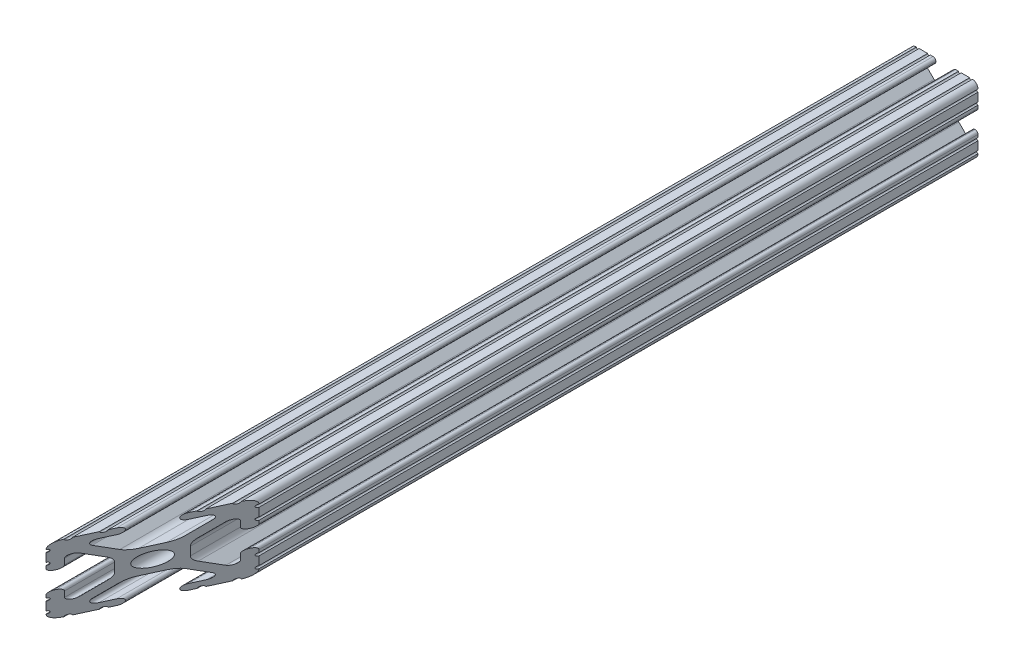
SolidWorks part; units mm, degrees
ref_plane "Front Plane" through (0, 0, 0) normal (0, 0, 1) x (1, 0, 0)
ref_plane "Top Plane" through (0, 0, 0) normal (0, 1, 0) x (1, 0, 0)
ref_plane "Right Plane" through (0, 0, 0) normal (1, 0, 0) x (0, 0, -1)
sketch "Sketch1" plane through (0, 0, 0) normal (0, 0, 1) x (1, 0, 0)
  line L88 (-7.1797, -8.6452) -> (-3.9523, -5.4237)
  line L89 (-1.7093, -4.4958) -> (1.7093, -4.4958)
  line L90 (3.9523, -5.4237) -> (7.1797, -8.6452)
  line L91 (6.4164, -10.4902) -> (4.2875, -10.4902)
  line L92 (3.2385, -11.5392) -> (3.2385, -11.651)
  line L93 (4.2875, -12.7) -> (5.3171, -12.7)
  line L94 (6.3331, -12.7) -> (9.5504, -12.7)
  line L95 (12.7, -9.5504) -> (12.7, -6.3331)
  line L96 (12.7, -5.3171) -> (12.7, -4.2875)
  line L97 (11.651, -3.2385) -> (11.5392, -3.2385)
  line L98 (10.4902, -4.2875) -> (10.4902, -6.4021)
  line L99 (8.7371, -7.1294) -> (5.441, -3.8408)
  line L100 (4.5085, -1.5932) -> (4.5085, 1.5932)
  line L101 (5.441, 3.8408) -> (8.7371, 7.1294)
  line L102 (10.4902, 6.4021) -> (10.4902, 4.2875)
  line L103 (11.5392, 3.2385) -> (11.651, 3.2385)
  line L104 (12.7, 4.2875) -> (12.7, 5.3171)
  line L105 (12.7, 6.3331) -> (12.7, 9.5504)
  line L106 (9.5504, 12.7) -> (6.3331, 12.7)
  line L107 (5.3171, 12.7) -> (4.2875, 12.7)
  line L108 (3.2385, 11.651) -> (3.2385, 11.5392)
  line L109 (4.2875, 10.4902) -> (6.4768, 10.4902)
  line L110 (7.207, 8.7244) -> (3.8983, 5.4232)
  line L111 (1.6558, 4.4958) -> (-1.6558, 4.4958)
  line L112 (-3.8983, 5.4232) -> (-7.207, 8.7244)
  line L113 (-6.4768, 10.4902) -> (-4.2875, 10.4902)
  line L114 (-3.2385, 11.5392) -> (-3.2385, 11.651)
  line L115 (-4.2875, 12.7) -> (-5.3171, 12.7)
  line L116 (-6.3331, 12.7) -> (-9.5504, 12.7)
  line L117 (-12.7, 9.5504) -> (-12.7, 6.3331)
  line L118 (-12.7, 5.3171) -> (-12.7, 4.2875)
  line L119 (-11.651, 3.2385) -> (-11.5392, 3.2385)
  line L120 (-10.4902, 4.2875) -> (-10.4902, 6.4021)
  line L121 (-8.7371, 7.1294) -> (-5.441, 3.8408)
  line L122 (-4.5085, 1.5932) -> (-4.5085, -1.5932)
  line L123 (-5.441, -3.8408) -> (-8.7371, -7.1294)
  line L124 (-10.4902, -6.4021) -> (-10.4902, -4.2875)
  line L125 (-11.5392, -3.2385) -> (-11.651, -3.2385)
  line L126 (-12.7, -4.2875) -> (-12.7, -5.3171)
  line L127 (-12.7, -6.3331) -> (-12.7, -9.5504)
  line L128 (-9.5504, -12.7) -> (-6.3331, -12.7)
  line L129 (-5.3171, -12.7) -> (-4.2875, -12.7)
  line L130 (-3.2385, -11.651) -> (-3.2385, -11.5392)
  line L131 (-4.2875, -10.4902) -> (-6.4164, -10.4902)
  circle A1 centre (0, 0) radius 2.6035
  arc A104 (-7.1797, -8.6452) -> (-6.4164, -10.4902) centre (-6.4164, -9.4098) ccw
  arc A105 (-1.7093, -4.4958) -> (-3.9523, -5.4237) centre (-1.7093, -7.6708) ccw
  arc A106 (3.9523, -5.4237) -> (1.7093, -4.4958) centre (1.7093, -7.6708) ccw
  arc A107 (6.4164, -10.4902) -> (7.1797, -8.6452) centre (6.4164, -9.4098) ccw
  arc A108 (4.2875, -10.4902) -> (3.2385, -11.5392) centre (4.2875, -11.5392) ccw
  arc A109 (3.2385, -11.651) -> (4.2875, -12.7) centre (4.2875, -11.651) ccw
  arc A110 (6.3331, -12.7) -> (5.3171, -12.7) centre (5.8251, -12.7) ccw
  arc A111 (10.5664, -12.6998) -> (9.5504, -12.7) centre (10.0584, -12.7) ccw
  arc A112 (10.5664, -12.6998) -> (12.6998, -10.5664) centre (10.5918, -10.5918) ccw
  arc A113 (12.7, -9.5504) -> (12.6998, -10.5664) centre (12.7, -10.0584) ccw
  arc A114 (12.7, -5.3171) -> (12.7, -6.3331) centre (12.7, -5.8251) ccw
  arc A115 (12.7, -4.2875) -> (11.651, -3.2385) centre (11.651, -4.2875) ccw
  arc A116 (11.5392, -3.2385) -> (10.4902, -4.2875) centre (11.5392, -4.2875) ccw
  arc A117 (8.7371, -7.1294) -> (10.4902, -6.4021) centre (9.4628, -6.4021) ccw
  arc A118 (4.5085, -1.5932) -> (5.441, -3.8408) centre (7.6835, -1.5932) ccw
  arc A119 (5.441, 3.8408) -> (4.5085, 1.5932) centre (7.6835, 1.5932) ccw
  arc A120 (10.4902, 6.4021) -> (8.7371, 7.1294) centre (9.4628, 6.4021) ccw
  arc A121 (10.4902, 4.2875) -> (11.5392, 3.2385) centre (11.5392, 4.2875) ccw
  arc A122 (11.651, 3.2385) -> (12.7, 4.2875) centre (11.651, 4.2875) ccw
  arc A123 (12.7, 6.3331) -> (12.7, 5.3171) centre (12.7, 5.8251) ccw
  arc A124 (12.6998, 10.5664) -> (12.7, 9.5504) centre (12.7, 10.0584) ccw
  arc A125 (12.6998, 10.5664) -> (10.5664, 12.6998) centre (10.5918, 10.5918) ccw
  arc A126 (9.5504, 12.7) -> (10.5664, 12.6998) centre (10.0584, 12.7) ccw
  arc A127 (5.3171, 12.7) -> (6.3331, 12.7) centre (5.8251, 12.7) ccw
  arc A128 (4.2875, 12.7) -> (3.2385, 11.651) centre (4.2875, 11.651) ccw
  arc A129 (3.2385, 11.5392) -> (4.2875, 10.4902) centre (4.2875, 11.5392) ccw
  arc A130 (7.207, 8.7244) -> (6.4768, 10.4902) centre (6.4768, 9.4563) ccw
  arc A131 (1.6558, 4.4958) -> (3.8983, 5.4232) centre (1.6558, 7.6708) ccw
  arc A132 (-3.8983, 5.4232) -> (-1.6558, 4.4958) centre (-1.6558, 7.6708) ccw
  arc A133 (-6.4768, 10.4902) -> (-7.207, 8.7244) centre (-6.4768, 9.4563) ccw
  arc A134 (-4.2875, 10.4902) -> (-3.2385, 11.5392) centre (-4.2875, 11.5392) ccw
  arc A135 (-3.2385, 11.651) -> (-4.2875, 12.7) centre (-4.2875, 11.651) ccw
  arc A136 (-6.3331, 12.7) -> (-5.3171, 12.7) centre (-5.8251, 12.7) ccw
  arc A137 (-10.5664, 12.6998) -> (-9.5504, 12.7) centre (-10.0584, 12.7) ccw
  arc A138 (-10.5664, 12.6998) -> (-12.6998, 10.5664) centre (-10.5918, 10.5918) ccw
  arc A139 (-12.7, 9.5504) -> (-12.6998, 10.5664) centre (-12.7, 10.0584) ccw
  arc A140 (-12.7, 5.3171) -> (-12.7, 6.3331) centre (-12.7, 5.8251) ccw
  arc A141 (-12.7, 4.2875) -> (-11.651, 3.2385) centre (-11.651, 4.2875) ccw
  arc A142 (-11.5392, 3.2385) -> (-10.4902, 4.2875) centre (-11.5392, 4.2875) ccw
  arc A143 (-8.7371, 7.1294) -> (-10.4902, 6.4021) centre (-9.4628, 6.4021) ccw
  arc A144 (-4.5085, 1.5932) -> (-5.441, 3.8408) centre (-7.6835, 1.5932) ccw
  arc A145 (-5.441, -3.8408) -> (-4.5085, -1.5932) centre (-7.6835, -1.5932) ccw
  arc A146 (-10.4902, -6.4021) -> (-8.7371, -7.1294) centre (-9.4628, -6.4021) ccw
  arc A147 (-10.4902, -4.2875) -> (-11.5392, -3.2385) centre (-11.5392, -4.2875) ccw
  arc A148 (-11.651, -3.2385) -> (-12.7, -4.2875) centre (-11.651, -4.2875) ccw
  arc A149 (-12.7, -6.3331) -> (-12.7, -5.3171) centre (-12.7, -5.8251) ccw
  arc A150 (-12.6998, -10.5664) -> (-12.7, -9.5504) centre (-12.7, -10.0584) ccw
  arc A151 (-12.6998, -10.5664) -> (-10.5664, -12.6998) centre (-10.5918, -10.5918) ccw
  arc A152 (-9.5504, -12.7) -> (-10.5664, -12.6998) centre (-10.0584, -12.7) ccw
  arc A153 (-5.3171, -12.7) -> (-6.3331, -12.7) centre (-5.8251, -12.7) ccw
  arc A154 (-4.2875, -12.7) -> (-3.2385, -11.651) centre (-4.2875, -11.651) ccw
  arc A155 (-3.2385, -11.5392) -> (-4.2875, -10.4902) centre (-4.2875, -11.5392) ccw
extrude "Boss-Extrude1" add sketch "Sketch1" along normal mid plane 381
sketch "Sketch2" plane through (0, 12.7, 0) normal (0, 1, 0) x (1, 0, 0)
  line L0 (-12.7, -190.5) -> (-12.7, 190.5) construction
  line L1 (-6.3331, -190.5) -> (-9.5504, -190.5) construction
  line L2 (9.5504, -190.5) -> (6.3331, -190.5) construction
  line L3 (12.7, -190.5) -> (12.7, 190.5) construction
  line L4 (-12.7, -190.5) -> (-12.7, 190.5) construction
  line L5 (-6.3331, -190.5) -> (-9.5504, -190.5) construction
  line L6 (9.5504, -190.5) -> (6.3331, -190.5) construction
  line L7 (12.7, -190.5) -> (12.7, 190.5) construction
  line L8 (12.7, -190.5) -> (-12.7, -190.5)
  line L9 (-12.7, -190.5) -> (-12.7, -136.2099)
  line L10 (-12.7, -136.2099) -> (12.7, -81.0967)
  line L11 (12.7, -81.0967) -> (12.7, -190.5)
  line L12 (4.8768, -104.14) -> (-62.4332, -250.19) construction
  line L13 (4.8768, -104.14) -> (-62.4332, -250.19) construction
  dimension "D1" = 5.08
extrude "Cut-Extrude1" cut sketch "Sketch2" against normal through all
